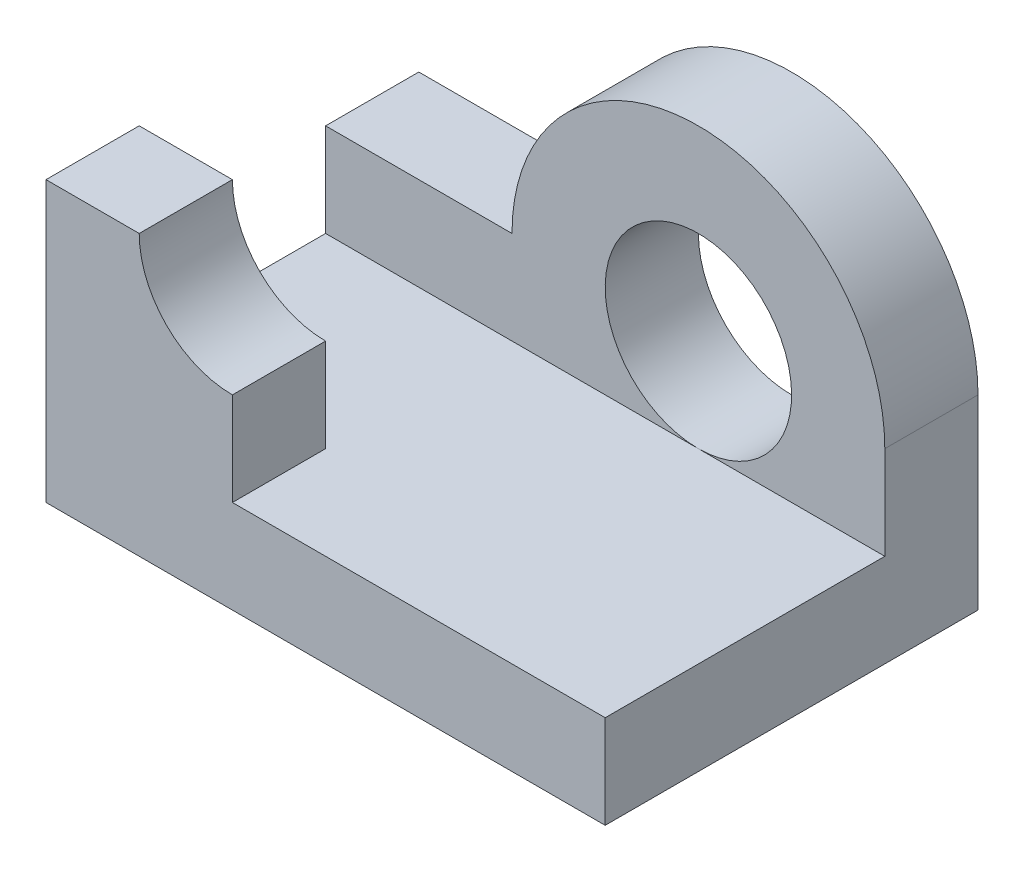
SolidWorks part; units mm, degrees
ref_plane "前基準面" through (0, 0, 0) normal (0, 0, 1) x (1, 0, 0)
ref_plane "上基準面" through (0, 0, 0) normal (0, 1, 0) x (1, 0, 0)
ref_plane "右基準面" through (0, 0, 0) normal (1, 0, 0) x (0, 0, -1)
sketch "草圖1" plane through (0, 0, 0) normal (0, 0, 1) x (1, 0, 0)
  line L0 (0, 0) -> (0, 25.6468) construction
  line L1 (0, 0) -> (-47.5247, 0) construction
  line L2 (-3.1085, 10) -> (12.6521, 10) construction
  line L3 (10, 10) -> (10, 0)
  line L4 (10, 0) -> (-20, 0)
  line L5 (-20, 0) -> (-20, 15)
  line L6 (-20, 15) -> (-15, 15)
  line L7 (-10, 5) -> (10, 5)
  line L9 (-10, 10) -> (-10, 0)
  line L10 (-10, 10) -> (-20, 10)
  line L11 (-20, 5) -> (-10, 5)
  circle A0 centre (0, 10) radius 5
  arc A1 (10, 10) -> (-10, 10) centre (0, 10) ccw
  arc A2 (-15, 15) -> (-10, 10) centre (-10, 15) ccw
  dimension "D1" = 10
  dimension "D3" = 20
  dimension "D9" = 5
  dimension "D2" = 10
  dimension "D4" = 30
  dimension "D5" = 15
  dimension "D6" = 5
  dimension "D7" = 5
  dimension "D8" = 10
extrude "填料-伸長1" add sketch "草圖1" along normal blind 5 contours L7 L9 L4 L3 | L3 A1 L9 L7 A0 | L11 L5 L4 L9 | L5 L11 L9 L10 region at (9.75, 7.5, 0) region at (0, 2.5, 0) region at (-15, 7.5, 0) region at (-15, 2.5, 0)
extrude "填料-伸長3" add sketch "草圖1<6>" along normal blind 20 contours L7 L9 L4 L3 | L11 L5 L4 L9 region at (0, 2.5, 0) region at (-15, 2.5, 0)
sketch "草圖1<6>" plane through (0, 0, 0) normal (0, 0, 1) x (1, 0, 0) same geometry as "草圖1"
extrude "填料-伸長4" add sketch "草圖1<7>" along normal blind 5 from offset 15 contours A2 L6 L5 L10 | L5 L11 L9 L10 region at (-15, 7.5, 0) region at (-16.861, 12.2556, 0)
sketch "草圖1<7>" plane through (0, 0, 0) normal (0, 0, 1) x (1, 0, 0) same geometry as "草圖1"
